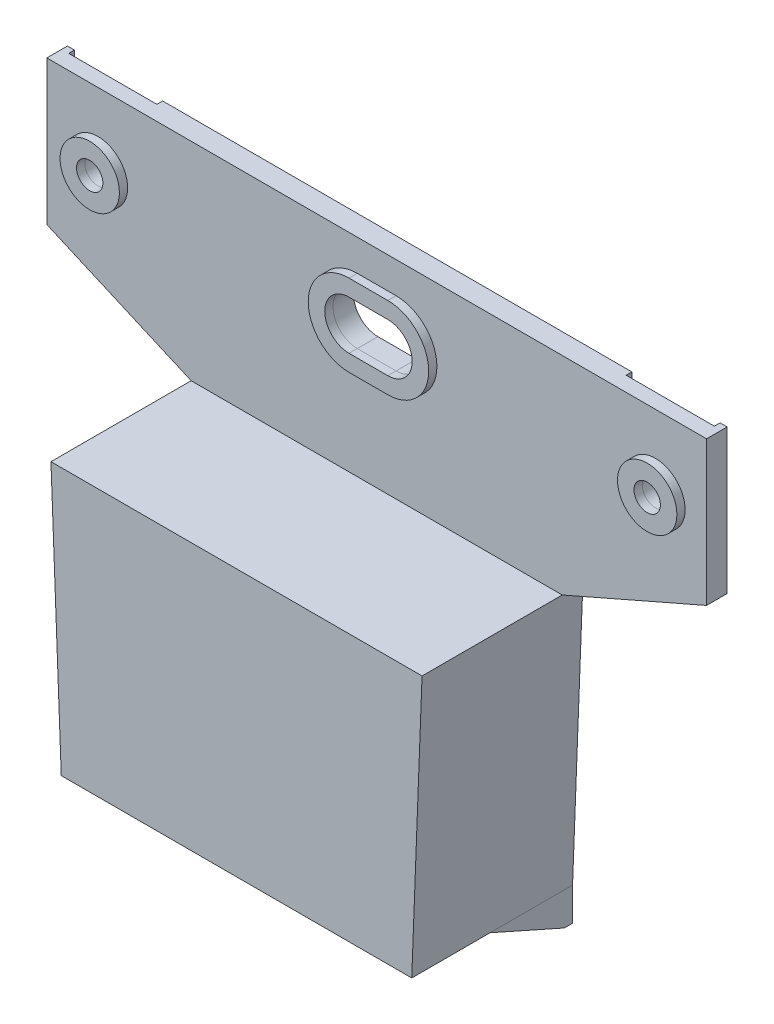
SolidWorks part; units mm, degrees
note: The reader was unsure of these and kept them because the rebuilt part matched: shared geometry of "Sketch17<2>".
ref_plane "Front Plane" through (0, 0, 0) normal (0, 0, 1) x (1, 0, 0)
ref_plane "Top Plane" through (0, 0, 0) normal (0, 1, 0) x (1, 0, 0)
ref_plane "Right Plane" through (0, 0, 0) normal (1, 0, 0) x (0, 0, -1)
sketch "Sketch1" plane through (0, 0, 0) normal (0, 0, 1) x (1, 0, 0)
  line L0 (-53.975, 0) -> (53.975, 0)
  line L1 (53.975, 0) -> (57.15, 82.1613)
  line L2 (57.15, 82.1613) -> (101.6, 101.6)
  line L3 (101.6, 101.6) -> (101.6, 146.05)
  line L4 (101.6, 146.05) -> (-101.6, 146.05)
  line L5 (-101.6, 146.05) -> (-101.6, 101.6)
  line L6 (-101.6, 101.6) -> (-57.15, 82.1613)
  line L7 (-57.15, 82.1613) -> (-53.975, 0)
  point P4 (0, 0)
  point P7 (99.2106, 80.5448)
  point P11 (150.9802, 108.9948)
  point P12 (168.7031, 179.4201)
  point P13 (122.5302, 64.6875)
  point P14 (-141.9146, 162.63)
  point P15 (160.7744, 159.3652)
  point P16 (0, 146.05)
  point P17 (106.1357, 84.2211)
  point P18 (-52.5891, 73.4875)
  point P19 (47.625, 73.4875)
  point P20 (0, 0)
  point P21 (0, 0)
  point P22 (0, 0)
  point P23 (59.5135, 63.148)
  point P24 (47.625, 76.7527)
  point P25 (-55.31, 74.0317)
  point P26 (52.4391, 58.7945)
  point P27 (57.881, 62.6038)
  point P28 (-62.8651, 60.7974)
  point P29 (-55.5161, 65.8234)
  point P30 (0, 0)
  point P31 (-57.15, 76.9651)
  point P32 (-57.15, 75.6023)
  point P33 (0, 0)
  point P34 (-62.7354, 72.9443)
  point P35 (0, 0)
  point P36 (0, 0)
  point P37 (57.15, 76.3201)
  point P38 (-57.15, 71.2353)
  point P39 (0, 0)
  point P40 (57.15, 83.2401)
  dimension "D1" = 44.45
  dimension "D2" = 44.45
  dimension "D3" = 146.05
  dimension "D4" = 107.95
  dimension "D5" = 203.2
  dimension "D6" = 114.3
base flange "Main Body" sketch "Sketch1" thickness 6.35 reverse thickness direction no parameters "D1"=1
sketch "Sketch6" plane through (0, 0, 0) normal (0, 0, 1) x (1, 0, 0)
  line L0 (53.975, 0) -> (-53.975, 0)
  line L1 (-53.975, 0) -> (-57.15, 82.1613)
  line L2 (-57.15, 82.1613) -> (57.15, 82.1613)
  line L3 (57.15, 82.1613) -> (53.975, 0)
  line L9 (-53.975, 0) -> (53.975, 0) construction
  point P4 (47.625, 0)
  point P6 (0, 0)
  point P7 (-48.5193, 74.822)
  point P8 (47.625, 0)
  point P10 (0, 0)
  point P11 (0, 82.1613)
  point P13 (-47.625, 0)
  point P14 (-57.15, 75.6023)
  point P15 (-50.6556, 74.8545)
  point P18 (57.15, 75.6023)
  dimension "D1" = 107.95
extrude "Pocket-Outer Surface" add sketch "Sketch6" along normal blind 43.18
sketch "Sketch7" plane through (0, 0, -6.35) normal (0, 0, -1) x (-1, 0, 0)
  line L0 (-50.5649, 76.2) -> (-47.8656, 6.35)
  line L1 (-47.8656, 6.35) -> (47.8656, 6.35)
  line L2 (47.8656, 6.35) -> (50.5649, 76.2)
  line L3 (50.5649, 76.2) -> (-50.5649, 76.2)
  line L5 (53.975, 0) -> (-53.975, 0) construction
  line L6 (57.15, 82.1613) -> (53.975, 0) construction
  line L7 (-53.975, 0) -> (-57.15, 82.1613) construction
  point P2 (0, 6.35)
  point P5 (0, 76.2)
  dimension "D1" = 6.35
  dimension "D2" = 6.35
  dimension "D3" = 69.85
extrude "Pocket-Inside" cut sketch "Sketch7" against normal blind 44.45 normal cut yes
sketch "Sketch8" plane through (0, 0, 0) normal (0, -1, 0) x (1, 0, 0)
  line L0 (-53.975, 19.05) -> (-53.975, -6.35)
  line L1 (-53.975, -6.35) -> (-53.975, 43.18) construction
  line L2 (-53.975, -6.35) -> (-43.815, -6.35)
  line L3 (-53.975, -6.35) -> (53.975, -6.35) construction
  line L4 (-43.815, -6.35) -> (-43.815, 19.05)
  line L5 (-43.815, 19.05) -> (-53.975, 19.05)
  dimension "D1" = 10.16
  dimension "D2" = 25.4
extrude "Bottom Screw Mount" add sketch "Sketch8" along normal blind 10.16
sketch "Sketch9" plane through (-53.975, 0, 0) normal (-1, 0, 0) x (0, 0, 1)
  line L0 (-3.81, -10.16) -> (19.05, -10.16)
  line L1 (19.05, -10.16) -> (19.05, 0)
  line L2 (19.05, 0) -> (-3.81, -10.16)
  point P4 (-6.35, -10.16)
  dimension "D1" = 22.86
extrude "Bottom Screw Mount Extrusion" cut sketch "Sketch9" against normal blind 10.16 normal cut yes
mirror "Left Bottom Screw Mount" about plane through (0, 0, 0) normal (1, 0, 0) of "Bottom Screw Mount Extrusion", "Bottom Screw Mount"
sketch "Sketch17" plane through (0, 0, 0) normal (0, 0, 1) x (1, 0, 0)
  line L0 (-5.969, 131.318) -> (5.969, 131.318)
  line L1 (5.969, 116.332) -> (-5.969, 116.332)
  line L2 (101.6, 146.05) -> (-101.6, 146.05) construction
  arc A0 (5.969, 131.318) -> (5.969, 116.332) centre (5.969, 123.825) cw
  arc A1 (-5.969, 116.332) -> (-5.969, 131.318) centre (-5.969, 123.825) cw
  circle A2 centre (85.852, 123.825) radius 4.064
  circle A3 centre (-85.852, 123.825) radius 4.064
  point P5 (1.524, 123.825)
  point P7 (-1.524, 123.825)
  point P8 (0, 131.318)
  point P9 (0, 116.332)
  point P12 (0, 146.05)
  point P15 (-13.462, 123.825)
  point P16 (13.462, 123.825)
  point P19 (-73.6283, 125.4447)
  point P20 (0, 0)
  point P21 (0, 0)
  dimension "D4" = 72.39
  dimension "D1" = 26.924
  dimension "D2" = 14.986
  dimension "D3" = 14.732
  dimension "D5" = 72.39
extrude "Light Sockets" cut sketch "Sketch17" against normal blind 6.35 and the other way through all normal cut yes
sketch "Sketch18" plane through (0, 0, 0) normal (0, 0, 1) x (1, 0, 0)
  line L10 (5.969, 136.398) -> (-5.969, 136.398)
  line L11 (5.969, 136.398) -> (-5.969, 136.398)
  line L13 (-5.969, 111.252) -> (5.969, 111.252)
  line L14 (-5.969, 111.252) -> (5.969, 111.252)
  arc A4 (5.969, 111.252) -> (5.969, 136.398) centre (5.969, 123.825) ccw
  arc A5 (-5.969, 136.398) -> (-5.969, 111.252) centre (-5.969, 123.825) ccw
  arc A6 (5.969, 111.252) -> (5.969, 136.398) centre (5.969, 123.825) ccw
  arc A7 (-5.969, 136.398) -> (-5.969, 111.252) centre (-5.969, 123.825) ccw
  circle A12 centre (-85.852, 123.825) radius 9.144
  circle A13 centre (-85.852, 123.825) radius 9.144
  circle A15 centre (85.852, 123.825) radius 9.144
  circle A16 centre (85.852, 123.825) radius 9.144
  dimension "D1" = 5.08
  dimension "D2" = 5.08
  dimension "D3" = 5.08
  dimension "D4" = 5.08
extrude "Light Lip Liners" add sketch "Sketch18" along normal blind 2.54
extrude "Light Lip Sockets" cut sketch "Sketch17<2>" along normal up to next normal cut yes
sketch "Sketch17<2>" plane through (0, 0, 0) normal (0, 0, 1) x (1, 0, 0) same geometry as "Sketch17"
sketch "Sketch19" plane through (0, 0, -6.35) normal (0, 0, -1) x (-1, 0, 0)
  line L0 (72.263, 146.05) -> (72.263, 123.825)
  line L1 (-101.6, 146.05) -> (101.6, 146.05) construction
  line L2 (99.441, 123.825) -> (99.441, 146.05)
  line L3 (99.441, 146.05) -> (72.263, 146.05)
  arc A0 (72.263, 123.825) -> (99.441, 123.825) centre (85.852, 123.825) ccw
  circle A1 centre (85.852, 123.825) radius 4.064 construction
  point P6 (84.7532, 122.728)
  point P8 (0, 0)
  point P9 (84.1227, 121.1288)
  point P10 (0, 0)
  dimension "D1" = 27.178
extrude "Tab Slots" cut sketch "Sketch19" against normal blind 1.778 normal cut yes
mirror "Mirror3" about plane through (0, 0, 0) normal (1, 0, 0) of "Tab Slots"
sketch "Bend-Lines1" [suppressed] plane through (0, 0, 0) normal (0, 1, 0) x (1, 0, 0)
sketch "Bounding-Box1" [suppressed] plane through (0, 0, 0) normal (0, 1, 0) x (1, 0, 0)
sheet metal parameters "Sheet-Metal1" thickness 6.35 parameters "D1"=1
flat pattern "Flat-Pattern1" [suppressed]
sketch "Bend-Lines2" plane through (0, 0, 0) normal (0, 1, 0) x (1, 0, 0)
sketch3d "Bounding-Box2" [suppressed]
  line L0 (101.6, 0, 0) -> (-101.6, 0, 0) construction
  line L1 (101.6, 146.05, 0) -> (-101.6, 146.05, 0) construction
  line L2 (101.6, 0, 0) -> (101.6, 146.05, 0) construction
  line L3 (-101.6, 0, 0) -> (-101.6, 146.05, 0) construction
sheet metal parameters "Sheet-Metal2" thickness 6.35 parameters "D1"=1
flat pattern "Flat-Pattern1"
sketch "Bend-Lines2" plane through (0, 0, 0) normal (0, 1, 0) x (1, 0, 0)
sketch3d "Bounding-Box2" [suppressed]
  line L0 (-101.6, 75.6023, 0) -> (101.6, 75.6023, 0) construction
  line L1 (-101.6, 146.05, 0) -> (101.6, 146.05, 0) construction
  line L2 (-101.6, 75.6023, 0) -> (-101.6, 146.05, 0) construction
  line L3 (101.6, 75.6023, 0) -> (101.6, 146.05, 0) construction
sheet metal parameters "Sheet-Metal3" thickness 6.35 parameters "D1"=1
flat pattern "Flat-Pattern1"
sketch "Bend-Lines2" plane through (0, 0, 0) normal (0, 1, 0) x (1, 0, 0)
sketch3d "Bounding-Box2" [suppressed]
  line L0 (-101.6, 81.9986, 0) -> (101.6, 81.9986, 0) construction
  line L1 (-101.6, 146.05, 0) -> (101.6, 146.05, 0) construction
  line L2 (-101.6, 81.9986, 0) -> (-101.6, 146.05, 0) construction
  line L3 (101.6, 81.9986, 0) -> (101.6, 146.05, 0) construction
sheet metal parameters "Sheet-Metal4" thickness 6.35 parameters "D1"=1
flat pattern "Flat-Pattern1"
sketch "Bend-Lines2" plane through (0, 0, 0) normal (0, 1, 0) x (1, 0, 0)
sketch3d "Bounding-Box2" [suppressed]
  line L0 (-101.6, 81.9986, 0) -> (101.6, 81.9986, 0) construction
  line L1 (-101.6, 146.05, 0) -> (101.6, 146.05, 0) construction
  line L2 (-101.6, 81.9986, 0) -> (-101.6, 146.05, 0) construction
  line L3 (101.6, 81.9986, 0) -> (101.6, 146.05, 0) construction
sheet metal parameters "Sheet-Metal5" thickness 6.35 parameters "D1"=1
flat pattern "Flat-Pattern1" [suppressed]
sketch "Bend-Lines2" plane through (0, 0, 0) normal (0, 1, 0) x (1, 0, 0)
sketch3d "Bounding-Box2" [suppressed]
  line L0 (-101.6, 81.9986, 0) -> (101.6, 81.9986, 0) construction
  line L1 (-101.6, 146.05, 0) -> (101.6, 146.05, 0) construction
  line L2 (-101.6, 81.9986, 0) -> (-101.6, 146.05, 0) construction
  line L3 (101.6, 81.9986, 0) -> (101.6, 146.05, 0) construction
sketch "Sketch10-1" [suppressed] plane through (0, 0, -6.35) normal (0, 0, -1) x (-1, 0, 0)
  circle A0 centre (42.545, -5.08) radius 2.286
sheet metal parameters "Sheet-Metal8" thickness 6.35 parameters "D1"=1
flat pattern "Flat-Pattern1"
sketch "Bend-Lines2" plane through (0, 0, 0) normal (0, 1, 0) x (1, 0, 0)
sketch3d "Bounding-Box2" [suppressed]
  line L0 (-101.6, 81.9986, 0) -> (101.6, 81.9986, 0) construction
  line L1 (-101.6, 146.05, 0) -> (101.6, 146.05, 0) construction
  line L2 (-101.6, 81.9986, 0) -> (-101.6, 146.05, 0) construction
  line L3 (101.6, 81.9986, 0) -> (101.6, 146.05, 0) construction
sheet metal parameters "Sheet-Metal9" thickness 6.35 parameters "D1"=1
flat pattern "Flat-Pattern1"
sketch "Bend-Lines2" plane through (0, 0, 0) normal (0, 1, 0) x (1, 0, 0)
sketch3d "Bounding-Box2" [suppressed]
  line L0 (-101.6, 81.9986, 0) -> (101.6, 81.9986, 0) construction
  line L1 (-101.6, 146.05, 0) -> (101.6, 146.05, 0) construction
  line L2 (-101.6, 81.9986, 0) -> (-101.6, 146.05, 0) construction
  line L3 (101.6, 81.9986, 0) -> (101.6, 146.05, 0) construction
sheet metal parameters "Sheet-Metal10" thickness 6.35 parameters "D1"=1
flat pattern "Flat-Pattern1"
sketch "Bend-Lines2" plane through (0, 0, 0) normal (0, 1, 0) x (1, 0, 0)
sketch3d "Bounding-Box2" [suppressed]
  line L0 (-101.6, 81.9986, 0) -> (101.6, 81.9986, 0) construction
  line L1 (-101.6, 146.05, 0) -> (101.6, 146.05, 0) construction
  line L2 (-101.6, 81.9986, 0) -> (-101.6, 146.05, 0) construction
  line L3 (101.6, 81.9986, 0) -> (101.6, 146.05, 0) construction
sheet metal parameters "Sheet-Metal11" thickness 6.35 parameters "D1"=1
flat pattern "Flat-Pattern1"
sketch "Bend-Lines2" plane through (0, 0, 0) normal (0, 1, 0) x (1, 0, 0)
sketch3d "Bounding-Box2" [suppressed]
  line L0 (-101.6, 81.9986, 0) -> (101.6, 81.9986, 0) construction
  line L1 (-101.6, 146.05, 0) -> (101.6, 146.05, 0) construction
  line L2 (-101.6, 81.9986, 0) -> (-101.6, 146.05, 0) construction
  line L3 (101.6, 81.9986, 0) -> (101.6, 146.05, 0) construction
sheet metal parameters "Sheet-Metal12" thickness 6.35 parameters "D1"=1
flat pattern "Flat-Pattern1"
sketch "Bend-Lines2" plane through (0, 0, 0) normal (0, 1, 0) x (1, 0, 0)
sketch3d "Bounding-Box2" [suppressed]
  line L0 (-101.6, 81.9986, 0) -> (101.6, 81.9986, 0) construction
  line L1 (-101.6, 146.05, 0) -> (101.6, 146.05, 0) construction
  line L2 (-101.6, 81.9986, 0) -> (-101.6, 146.05, 0) construction
  line L3 (101.6, 81.9986, 0) -> (101.6, 146.05, 0) construction
sheet metal parameters "Sheet-Metal13" thickness 6.35 parameters "D1"=1
flat pattern "Flat-Pattern1"
sketch "Bend-Lines2" plane through (0, 0, 0) normal (0, 1, 0) x (1, 0, 0)
sketch3d "Bounding-Box2" [suppressed]
  line L0 (-101.6, 82.1613, 0) -> (101.6, 82.1613, 0) construction
  line L1 (-101.6, 146.05, 0) -> (101.6, 146.05, 0) construction
  line L2 (-101.6, 82.1613, 0) -> (-101.6, 146.05, 0) construction
  line L3 (101.6, 82.1613, 0) -> (101.6, 146.05, 0) construction
